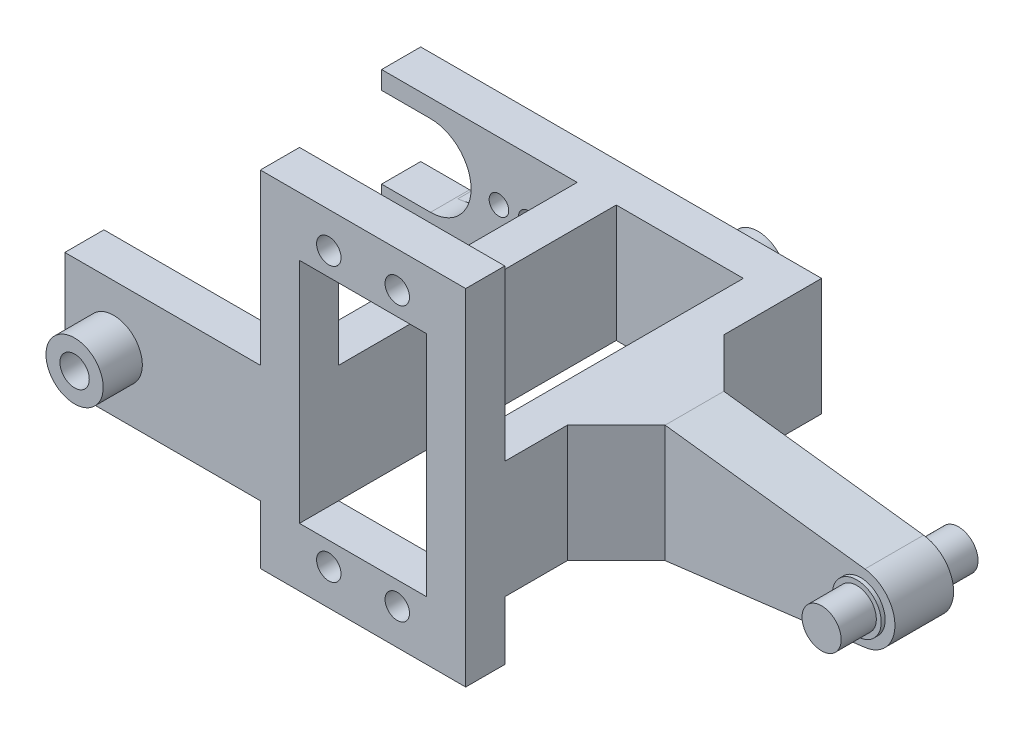
SolidWorks part; units mm, degrees
note: The reader was unsure of these and kept them because the rebuilt part matched: shared geometry of "草图6<3>".
ref_plane "前视基准面" through (0, 0, 0) normal (0, 0, 1) x (1, 0, 0)
ref_plane "上视基准面" through (0, 0, 0) normal (0, 1, 0) x (1, 0, 0)
ref_plane "右视基准面" through (0, 0, 0) normal (1, 0, 0) x (0, 0, -1)
other "Configuration Table"
sketch "草图1" plane through (0, 0, 0) normal (0, 1, 0) x (1, 0, 0)
  line L0 (0, 0) -> (20, 0)
  line L1 (20, 0) -> (20, 28.4)
  line L2 (20, 28.4) -> (0, 28.4)
  line L3 (0, 28.4) -> (0, 0) construction
  line L4 (0, -4) -> (24, -4)
  line L5 (24, -4) -> (24, 28.4)
  line L6 (24, 32.4) -> (0, 32.4)
  line L7 (0, 32.4) -> (0, 28.4)
  line L8 (0, 0) -> (0, -4)
  line L9 (24, 32.4) -> (41, 32.4)
  line L10 (41, 32.4) -> (41, -4)
  line L11 (24, 28.4) -> (37, 28.4)
  line L12 (37, 28.4) -> (37, -4)
  line L13 (37, -4) -> (41, -4)
  line L14 (24, 28.4) -> (24, 32.4) construction
  line L15 (24, -4) -> (24, 32.4) construction
  dimension "D1" = 20
  dimension "D2" = 28.4
  dimension "D5" = 13
  dimension "D3" = 4
  dimension "D4" = 4
extrude "凸台-拉伸1" add sketch "草图1" along normal blind 12
sketch "草图2" plane through (0, 0, 4) normal (0, 0, 1) x (1, 0, 0)
  line L0 (24, 6) -> (37, 6) construction
  line L1 (24, 12) -> (24, 0) construction
  line L2 (37, 12) -> (37, 0) construction
  line L3 (30.5, 6) -> (30.5, 11.65) construction
  line L4 (30.5, 29.3) -> (30.5, -6) construction
  line L5 (24, 23.3) -> (37, 23.3)
  line L6 (24, 23.3) -> (24, 0)
  line L7 (24, 0) -> (37, 0)
  line L8 (37, 23.3) -> (37, 0)
  line L9 (24, 23.3) -> (37, 0) construction
  line L10 (24, 0) -> (37, 23.3) construction
  line L11 (41, -6) -> (20, -6)
  line L12 (41, -6) -> (41, 29.3)
  line L13 (41, 29.3) -> (20, 29.3)
  line L14 (20, -6) -> (20, 29.3)
  line L15 (41, -6) -> (20, 29.3) construction
  line L16 (41, 29.3) -> (20, -6) construction
  line L17 (20, 11.65) -> (41, 11.65) construction
  circle A0 centre (27, 25.65) radius 1.25
  circle A1 centre (27, -2.35) radius 1.25
  circle A2 centre (34, -2.35) radius 1.25
  circle A3 centre (34, 25.65) radius 1.25
  dimension "D6" = 2.5
  dimension "D8" = 7
  dimension "D1" = 5.65
  dimension "D2" = 13
  dimension "D3" = 23.3
  dimension "D4" = 4
  dimension "D5" = 6
  dimension "D7" = 28
extrude "凸台-拉伸2" add sketch "草图2" against normal blind 4
sketch "草图3" plane through (0, 0, -32.4) normal (0, 0, -1) x (-1, 0, 0)
  line L0 (-41, 6) -> (-66, 6) construction
  line L1 (-41, 12) -> (-41, 0) construction
  line L2 (-41, 12) -> (-46, 12)
  line L3 (-46, 12) -> (-66.4296, 9.4735)
  line L4 (-46, 0) -> (-66.4296, 2.5265)
  line L5 (-41, 0) -> (-46, 0)
  line L6 (-41, 12) -> (-41, 0)
  arc A0 (-66.4296, 9.4735) -> (-66.4296, 2.5265) centre (-66, 6) ccw
  arc A1 (-62.5, 6) -> (-66.4296, 9.4735) centre (-66, 6) ccw construction
  arc A2 (-66.4296, 2.5265) -> (-62.5, 6) centre (-66, 6) ccw construction
  dimension "D2" = 3.5
  dimension "D1" = 5
  dimension "D3" = 25
extrude "凸台-拉伸3" add sketch "草图3" along normal mid plane 6 from offset 18 offset against normal yes
chamfer "倒角1" distance 5 angle 45 6 edges at (41, 6, -11.4) (43.5, 12, -11.4) (43.5, 0, -11.4) (41, 6, -17.4) (43.5, 12, -17.4) (43.5, 0, -17.4)
sketch "草图4" plane through (0, 0, -17.4) normal (0, 0, -1) x (-1, 0, 0)
  circle A0 centre (-66, 6) radius 2
  dimension "D1" = 4
extrude "凸台-拉伸4" add sketch "草图4" along normal mid plane 14 from offset 3 offset against normal yes
sketch "草图5" plane through (0, 0, -32.4) normal (0, 0, -1) x (-1, 0, 0)
  line L0 (0, 6) -> (-5, 6) construction
  line L1 (0, 12) -> (0, 0) construction
  line L2 (-5, 10.15) -> (0, 10.15)
  line L3 (0, 10.15) -> (0, 1.85)
  line L4 (-5, 1.85) -> (0, 1.85)
  circle A0 centre (-5, 6) radius 4.15
  dimension "D2" = 8.3
  dimension "D1" = 5
extrude "切除-拉伸1" cut sketch "草图5" against normal blind 12
sketch "草图6" plane through (0, 0, -32.4) normal (0, 0, -1) x (-1, 0, 0)
  line L0 (-5, 6) -> (-18, 6) construction
  line L1 (-5.2075, 10.1448) -> (-18.175, 9.4956)
  line L2 (-5.2075, 1.8552) -> (-18.175, 2.5044)
  circle A0 centre (-18, 6) radius 1
  circle A1 centre (-15, 6) radius 1
  circle A2 centre (-12, 6) radius 1
  circle A3 centre (-18, 6) radius 3.5
  arc A4 (-5, 10.15) -> (-5, 1.85) centre (-5, 6) ccw construction
  arc A5 (-5, 10.15) -> (-5, 1.85) centre (-5, 6) ccw
  dimension "D3" = 2
  dimension "D4" = 2
  dimension "D6" = 2
  dimension "D7" = 7
  dimension "D1" = 13
  dimension "D2" = 7
  dimension "D5" = 3
extrude "切除-拉伸2" cut sketch "草图6" against normal blind 1.4
extrude "切除-拉伸3" cut sketch "草图6<3>" against normal blind 4
sketch "草图6<3>" plane through (0, 0, -32.4) normal (0, 0, -1) x (-1, 0, 0) same geometry as "草图6"
sketch "草图7" plane through (0, 0, 4) normal (0, 0, 1) x (1, 0, 0)
  line L0 (0, 6) -> (5, 6) construction
  line L1 (0, 12) -> (0, 0) construction
  circle A0 centre (5, 6) radius 2.925
  dimension "D1" = 5.85
  dimension "D2" = 5
extrude "凸台-拉伸5" add sketch "草图7" along normal blind 4
sketch "草图8" plane through (0, 0, 8) normal (0, 0, 1) x (1, 0, 0)
  circle A0 centre (5, 6) radius 1.5
  dimension "D1" = 3
extrude "切除-拉伸4" cut sketch "草图8" against normal blind 5
sketch "草图9" plane through (0, 0, -32.4) normal (0, 0, -1) x (-1, 0, 0)
  line L0 (-41, 6) -> (-30.5, 6) construction
  line L1 (-41, 12) -> (-41, 0) construction
  circle A0 centre (-30.5, 6) radius 2.925
  dimension "D2" = 5.85
  dimension "D1" = 10.5
extrude "凸台-拉伸6" add sketch "草图9" along normal blind 4
sketch "草图10" plane through (0, 0, -36.4) normal (0, 0, -1) x (-1, 0, 0)
  circle A0 centre (-30.5, 6) radius 1.5
  dimension "D1" = 3
extrude "切除-拉伸5" cut sketch "草图10" against normal blind 5
sketch "草图11" plane through (0, 0, -17.4) normal (0, 0, -1) x (-1, 0, 0)
  circle A1 centre (-66, 6) radius 2.5
  dimension "D1" = 5
extrude "凸台-拉伸7" add sketch "草图11" along normal blind 0.4
sketch "草图12" plane through (0, 0, -11.4) normal (0, 0, 1) x (1, 0, 0)
  circle A0 centre (66, 6) radius 2.5
  dimension "D1" = 5
extrude "凸台-拉伸8" add sketch "草图12" along normal blind 0.4
ref_plane "基准面1" through (-10, 0, 0) normal (1, 0, 0) x (0, 0, -1)
